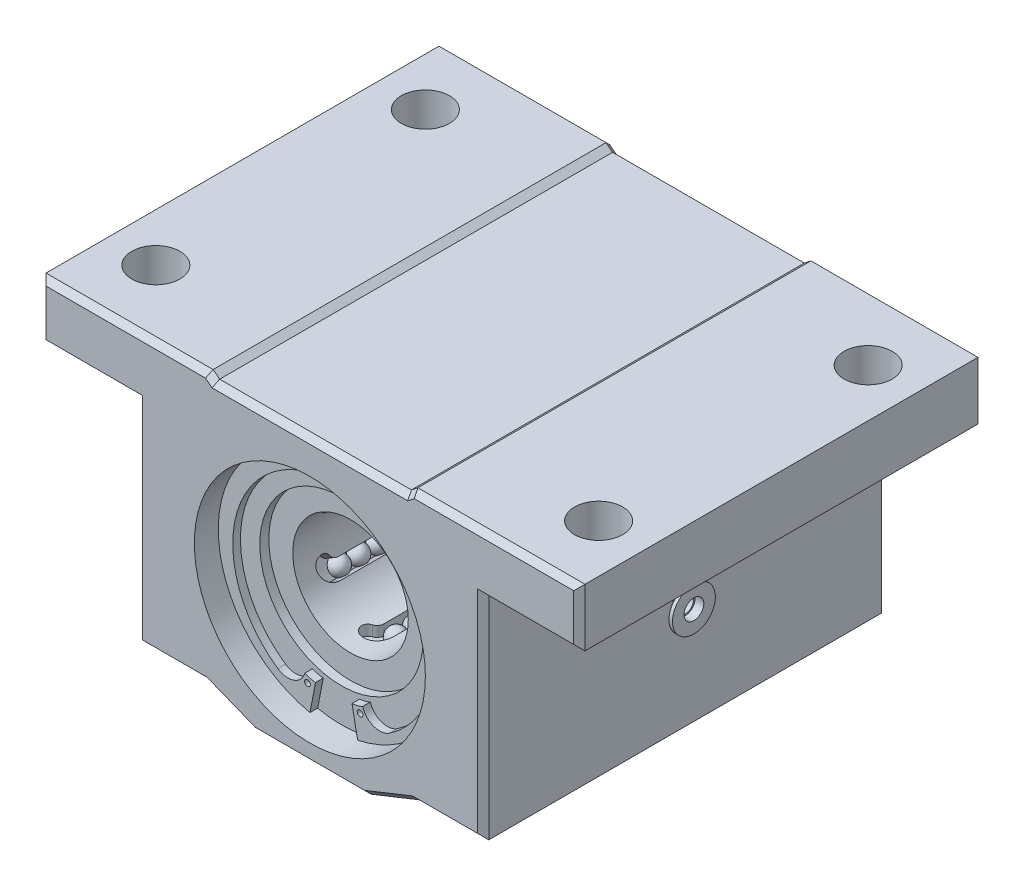
SolidWorks part; units mm, degrees
ref_plane "Front" through (0, 0, 0) normal (0, 0, 1) x (1, 0, 0)
ref_plane "Top" through (0, 0, 0) normal (0, 1, 0) x (1, 0, 0)
ref_plane "Right" through (0, 0, 0) normal (1, 0, 0) x (0, 0, -1)
sketch "Sketch1" plane through (0, 0, 0) normal (0, 0, 1) x (1, 0, 0)
  line L0 (0, 11.9062) -> (0, -11.9062) construction
  line L1 (-22.225, 11.9062) -> (-8.4455, 11.9062)
  line L2 (-22.225, 11.9062) -> (-22.225, 7.1437)
  line L3 (-22.225, 7.1437) -> (-14.2875, 7.1437)
  line L4 (-14.2875, 7.1437) -> (-14.2875, -10.3187)
  line L5 (-14.2875, -10.3187) -> (-8.5725, -10.3187)
  line L6 (-8.5725, -10.3187) -> (-4.5911, -11.9062)
  line L7 (-4.5911, -11.9062) -> (4.5911, -11.9062)
  line L8 (-8.4455, 11.9062) -> (-7.9065, 11.4829)
  line L9 (-7.9065, 11.4829) -> (7.9065, 11.4829)
  line L10 (8.4455, 11.9063) -> (7.9065, 11.4829)
  line L11 (8.5725, -10.3187) -> (4.5911, -11.9062)
  line L12 (14.2875, -10.3187) -> (8.5725, -10.3187)
  line L13 (14.2875, 7.1438) -> (14.2875, -10.3187)
  line L14 (22.225, 7.1438) -> (14.2875, 7.1438)
  line L15 (22.225, 11.9063) -> (22.225, 7.1438)
  line L16 (22.225, 11.9063) -> (8.4455, 11.9063)
  point P12 (0, 11.4829)
  dimension "MMC F " = 23.8125
  dimension "MMC H " = 4.7625
  dimension "Supplier M " = 28.575
  dimension "MMC D " = 44.45
  dimension "Supplier G " = 22.225
  dimension "D6" = 4.2862
  dimension "D7" = 5.715
  dimension "D8" = 15.8131
  dimension "D9" = 0.4233
  dimension "D10" = 13.7795
extrude "Extrude1" add sketch "Sketch1" along normal mid plane 33.3375
sketch "Sketch2" plane through (0, 0, 16.6687) normal (0, 0, 1) x (1, 0, 0)
  line L0 (22.225, 11.9063) -> (8.4455, 11.9063) construction
  line L1 (0, -50) -> (0, 50) construction
  line L2 (0, -11.9062) -> (0, -10.3188) construction
  line L3 (-4.5911, -11.9062) -> (4.5911, -11.9062) construction
  circle A0 centre (0, -0.7937) radius 9.525
  dimension "D2" = 19.05
  dimension "MMC G " = 12.7
extrude "Cut-Extrude1" cut sketch "Sketch2" against normal blind 2.6077
sketch "Sketch3" plane through (0, 0, 14.061) normal (0, 0, 1) x (1, 0, 0)
  line L0 (0, 0) -> (0, 23.0187) construction
  line L1 (0, -50) -> (0, 50) construction
  line L2 (0, 0) -> (0, 41.1582) construction
  line L3 (0, 0) -> (0, -10.3188) construction
  line L4 (0, 0) -> (-2.1699, -8.0983) construction
  line L5 (0, 0) -> (-1.9659, -10.1137) construction
  line L6 (-1.5021, -7.7278) -> (-1.9659, -10.1137)
  line L7 (0, 0) -> (1.9659, -10.1137) construction
  line L8 (0, 0) -> (2.1699, -8.0983) construction
  line L9 (1.5021, -7.7278) -> (1.9659, -10.1137)
  arc A0 (0, 7.345) -> (-4.6134, -8.2898) centre (0.2409, -1.2242) ccw
  circle A1 centre (0, -0.7937) radius 7.62 construction
  arc A2 (1.9659, -10.1137) -> (-1.9659, -10.1137) centre (0, -0.7937) ccw
  circle A3 centre (0, -0.7937) radius 9.525 construction
  circle A4 centre (0, -0.7937) radius 9.525 construction
  circle A5 centre (2.1699, -8.0983) radius 0.2381
  arc A6 (-4.6134, -8.2898) -> (-2.3825, -7.4965) centre (-3.7854, -7.0847) ccw
  arc A7 (-2.3825, -7.4965) -> (-1.5021, -7.7278) centre (-1.3484, -5.3515) ccw
  arc A8 (2.3825, -7.4965) -> (1.5021, -7.7278) centre (1.3484, -5.3515) cw
  arc A9 (4.6134, -8.2898) -> (2.3825, -7.4965) centre (3.7854, -7.0847) cw
  circle A10 centre (-2.1699, -8.0983) radius 0.2381
  arc A11 (0, 7.345) -> (4.6134, -8.2898) centre (-0.2409, -1.2242) cw
  dimension "D1" = 8.5725
  dimension "D4" = 1.4622
  dimension "D6" = 5.3515
  dimension "D7" = 1.3484
  dimension "D8" = 15.24
  dimension "D9" = 0.4763
  dimension "D10" = 15
  dimension "D12" = 2.3812
  dimension "D2" = 1.2242
  dimension "D3" = 0.2409
  dimension "D5" = 3.7854
  dimension "D11" = 11
sketch "Sketch4" plane through (0, 0, 14.061) normal (0, 0, 1) x (1, 0, 0)
  circle A0 centre (0, -0.7937) radius 6.7389
  circle A2 centre (0, -0.7937) radius 9.525 construction
  dimension "D1" = 13.4779
extrude "Cut-Extrude2" cut sketch "Sketch4" against normal blind 0.7451
mirror "Mirror1" about plane through (0, 0, 0) normal (0, 0, 1) of "Cut-Extrude2", "Cut-Extrude1"
sketch "Sketch5" plane through (0, 0, 13.3159) normal (0, 0, 1) x (1, 0, 0)
  circle A0 centre (0, -0.7937) radius 4.7625
  circle A1 centre (0, -0.7937) radius 6.7389 construction
  dimension "ID " = 9.525
extrude "Cut-Extrude3" cut sketch "Sketch5" against normal through all
ref_plane "Plane1" through (0, -0.7937, 0) normal (0, 1, 0) x (-1, 0, 0)
sketch "Sketch8" plane through (0, -0.7937, 0) normal (0, 1, 0) x (-1, 0, 0)
  line L0 (0, 13.3159) -> (0, -11.1142) construction
  line L1 (6.7389, 13.3159) -> (-6.7389, 13.3159) construction
  line L2 (0.6572, -9.5269) -> (0.6572, -8.2125) construction
  line L3 (0, 1.1009) -> (-22.225, 1.1009) construction
  line L4 (-22.225, 16.6687) -> (-22.225, -16.6687) construction
  line L5 (0.6572, 9.9006) -> (0.6572, -7.6988)
  line L6 (-0.6572, -8.2125) -> (0.6572, -8.2125) construction
  line L12 (-0.6572, -8.2125) -> (-0.6572, 10.4142)
  line L14 (-0.6572, 10.4142) -> (0.6572, 10.4142) construction
  line L15 (0.6572, 11.7287) -> (0.6572, 10.4142) construction
  line L16 (0, 0) -> (98.9742, 0) construction
  line L17 (50, 0) -> (-50, 0) construction
  line L20 (-7.9065, 16.6687) -> (7.9065, 16.6687) construction
  arc A0 (-0.6572, 10.4142) -> (0.6572, 11.7287) centre (0.6572, 10.4142) cw
  arc A1 (0.9995, 10.5104) -> (0.6572, 11.7287) centre (0.6572, 11.0714) ccw
  arc A2 (0.9995, 10.5104) -> (0.6572, 9.9006) centre (1.3716, 9.9006) ccw
  arc A3 (0.9995, -8.3086) -> (0.6572, -7.6988) centre (1.3716, -7.6988) cw
  arc A4 (0.9995, -8.3086) -> (0.6572, -9.5269) centre (0.6572, -8.8697) cw
  arc A5 (-0.6572, -8.2125) -> (0.6572, -9.5269) centre (0.6572, -8.2125) ccw
  point P8 (-0.6572, 1.1009)
  point P10 (0.6572, 1.1009)
  point P28 (-0.6572, 1.1009)
  point P30 (0.6572, 1.1009)
  dimension "D3" = 0.7144
  dimension "D4" = 0.6572
  dimension "D5" = 5.5973
  dimension "D1" = 1.3144
  dimension "D2" = 9.3133
extrude "Cut-Extrude4" cut sketch "Sketch8" against normal offset from surface (5.5705 mm away) 0.8467
pattern_circular "CirPattern1" count 6 over 360 about axis through (0, -0.7937, 0) along (0, 0, 1) of "Cut-Extrude4"
sketch "Sketch10" plane through (0, 0, 0) normal (0, 0, 1) x (1, 0, 0)
  line L0 (-0.6572, -5.5107) -> (-0.6572, -6.3643) construction
  line L1 (0.6572, -5.5107) -> (0.6572, -6.3643) construction
  line L2 (-0.6572, -6.3643) -> (0.6572, -6.3643) construction
  line L3 (-0.7763, -6.3325) -> (0.7763, -6.3325)
  circle A0 centre (0, -0.7937) radius 4.7625 construction
  circle A2 centre (0, -0.7937) radius 4.7625 construction
  arc A3 (0.7763, -6.3325) -> (-0.7763, -6.3325) centre (0, -6.3325) ccw
  dimension "D1" = 0.1191
  dimension "D2" = 0.1191
revolve "Revolve2" add sketch "Sketch10" angle 360 about L3
pattern_linear "LPattern1" count 7 spacing 1.5875 along (0, 0, 1) of "Revolve2"
mirror "Mirror5" about plane through (0, 0, 0) normal (0, 0, 1) of "Revolve2", "LPattern1"
pattern_circular "CirPattern2" count 6 over 360 about axis through (0, -0.7937, 0) along (0, 0, 1) of "Revolve2", "LPattern1", "Mirror5"
chamfer "Chamfer1" distance 0.4657 angle 45 32 edges at (14.2875, -1.5875, -16.6687) (11.43, -10.3187, -16.6687) (6.5818, -11.1125, -16.6687) (0, -11.9062, -16.6687) (-6.5818, -11.1125, -16.6687) (-11.43, -10.3187, -16.6687) (-14.2875, -1.5875, -16.6687) (-18.2562, 7.1437, -16.6687) (-22.225, 9.525, -16.6687) (-15.3352, 11.9062, -16.6687) (-8.176, 11.6946, -16.6687) (0, 11.4829, -16.6687) (8.176, 11.6946, -16.6687) (15.3352, 11.9063, -16.6687) (22.225, 9.525, -16.6687) (18.2562, 7.1438, -16.6687) (8.176, 11.6946, 16.6687) (0, 11.4829, 16.6687) (-8.176, 11.6946, 16.6687) (-15.3352, 11.9062, 16.6687) (-22.225, 9.525, 16.6687) (-18.2562, 7.1437, 16.6687) (-14.2875, -1.5875, 16.6687) (-11.43, -10.3187, 16.6687) (-6.5818, -11.1125, 16.6687) (0, -11.9062, 16.6687) (6.5818, -11.1125, 16.6687) (11.43, -10.3187, 16.6687) (14.2875, -1.5875, 16.6687) (18.2562, 7.1438, 16.6687) (22.225, 9.525, 16.6687) (15.3352, 11.9063, 16.6687)
sketch "Sketch11" plane through (14.2875, 0, 0) normal (1, 0, 0) x (0, 0, -1)
  line L0 (-16.2031, -1.5875) -> (16.2031, -1.5875) construction
  line L1 (-16.2031, 7.1438) -> (-16.2031, -10.3187) construction
  line L2 (16.2031, -10.3187) -> (16.2031, 7.1438) construction
  line L3 (0, -1.5875) -> (0, 11.9063) construction
  line L4 (-16.2031, 11.9063) -> (16.2031, 11.9063) construction
  circle A0 centre (0, -1.5875) radius 0.6985
  dimension "D1" = 1.397
extrude "Cut-Extrude5" cut sketch "Sketch11" against normal blind 0.9525
sketch "Sketch12" plane through (0, 0, 0) normal (0, 0, 1) x (1, 0, 0)
  line L0 (14.2875, -1.5875) -> (102.8363, -1.5875) construction
  line L1 (14.2875, -2.286) -> (14.2875, -0.889) construction
  line L2 (14.2875, -0.7726) -> (14.2875, -0.3768)
  line L3 (14.2875, 7.1438) -> (14.2875, -10.3187) construction
  line L4 (14.2875, -0.3768) -> (14.7161, -0.3768)
  line L5 (14.7161, -0.3768) -> (14.7161, 0.182)
  line L6 (14.7161, 0.182) -> (15.0019, 0.182)
  line L7 (15.0019, 0.182) -> (15.0019, -0.7726)
  line L8 (15.0019, -0.7726) -> (14.2875, -0.7726)
  dimension "D1" = 1.6298
  dimension "D2" = 3.5391
  dimension "D3" = 2.4215
  dimension "D4" = 0.2858
  dimension "D5" = 0.7144
revolve "Revolve3" add sketch "Sketch12" angle 360 about L0
sketch "Sketch13" plane through (0, 11.9062, 0) normal (0, 1, 0) x (1, 0, 0)
  line L0 (18.2563, 0) -> (-18.2562, 0) construction
  line L1 (-18.2562, 11.1125) -> (18.2562, 11.1125) construction
  line L2 (-18.2562, 11.1125) -> (-18.2562, -11.1125) construction
  line L3 (-18.2562, -11.1125) -> (18.2563, -11.1125) construction
  line L4 (18.2562, 11.1125) -> (18.2563, -11.1125) construction
  line L6 (0, 11.1125) -> (0, -11.1125) construction
  circle A0 centre (-18.2562, 11.1125) radius 1.9844
  circle A1 centre (18.2562, 11.1125) radius 1.9844
  circle A2 centre (18.2563, -11.1125) radius 1.9844
  circle A3 centre (-18.2562, -11.1125) radius 1.9844
  dimension "MMC L " = 3.9688
  dimension "MMC K " = 22.225
  dimension "MMC J " = 36.5125
extrude "Cut-Extrude6" cut sketch "Sketch13" against normal up to surface (4.7625 mm away) up to face at (18.2562, 7.1438, 0)
extrude "Extrude2" add sketch "Sketch3" along normal blind 0.635
mirror "Mirror4" about plane through (0, 0, 0) normal (0, 0, 1) of "Extrude2"
